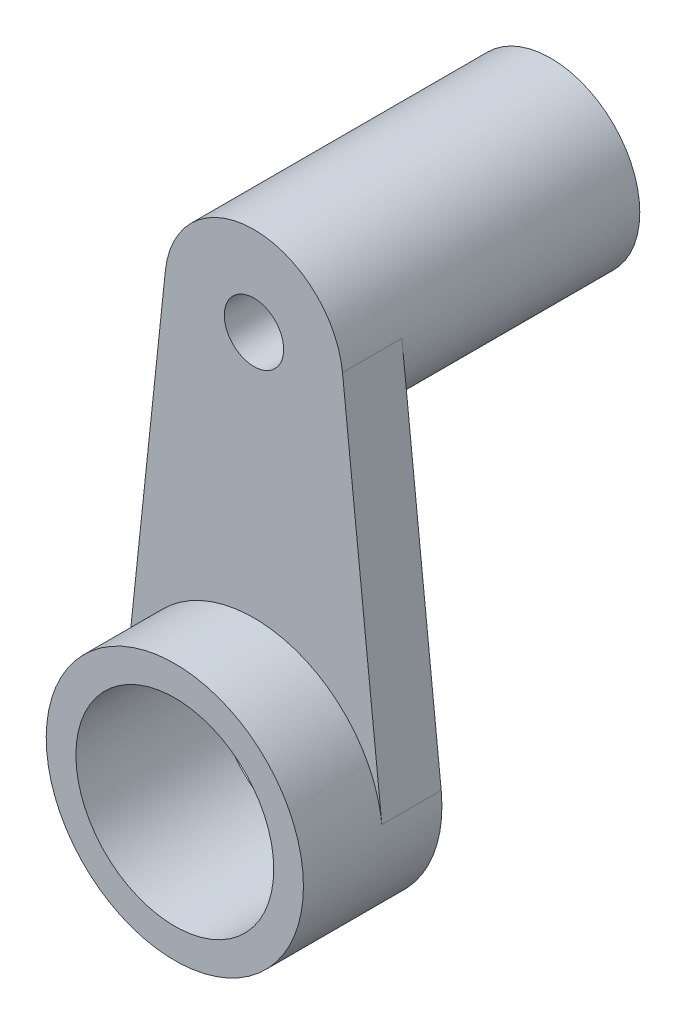
SolidWorks part; units mm, degrees
ref_plane "Front Plane" through (0, 0, 0) normal (1, 0, 0) x (0, 1, 0)
ref_plane "Top Plane" through (0, 0, 0) normal (0, 0, 1) x (0, 1, 0)
ref_plane "Right Plane" through (0, 0, 0) normal (0, 1, 0) x (-1, 0, 0)
sketch "Sketch2" plane through (0, 0, 0) normal (0, 0, 1) x (0, 1, 0)
  line L0 (1.3684, 12.9278) -> (38.9474, 8.95)
  line L1 (0, 0) -> (99.2892, 0) construction
  line L2 (1.3684, -12.9278) -> (38.9474, -8.95)
  arc A1 (1.3684, 12.9278) -> (1.3684, -12.9278) centre (0, 0) ccw
  arc A3 (38.9474, -8.95) -> (38.9474, 8.95) centre (38, 0) ccw
  dimension "D2" = 26
  dimension "D5" = 18
  dimension "D4" = 38
  dimension "D6" = 0
extrude "Boss-Extrude1" add sketch "Sketch2" along normal blind 6
sketch "Sketch3" plane through (0, 0, 0) normal (0, 0, 1) x (0, 1, 0)
  circle A0 centre (0, 0) radius 13
  dimension "D1" = 26
extrude "Boss-Extrude2" add sketch "Sketch3" along normal blind 8 from surface starting at face at (0, 18.5789, 6)
sketch "Sketch4" plane through (0, 0, 0) normal (0, 0, 1) x (0, 1, 0)
  circle A0 centre (38, 0) radius 9
  dimension "D2" = 18
  dimension "D1" = 38
extrude "Boss-Extrude3" add sketch "Sketch4" against normal blind 24 from surface starting at face at (0, 18.5789, 0)
sketch "Sketch5" plane through (0, 0, 0) normal (0, 0, 1) x (0, 1, 0)
  circle A0 centre (0, 0) radius 10
  circle A1 centre (38, 0) radius 3
  dimension "D1" = 20
  dimension "D2" = 38
  dimension "D3" = 6
extrude "Cut-Extrude1" cut sketch "Sketch5" against normal mid plane 60
